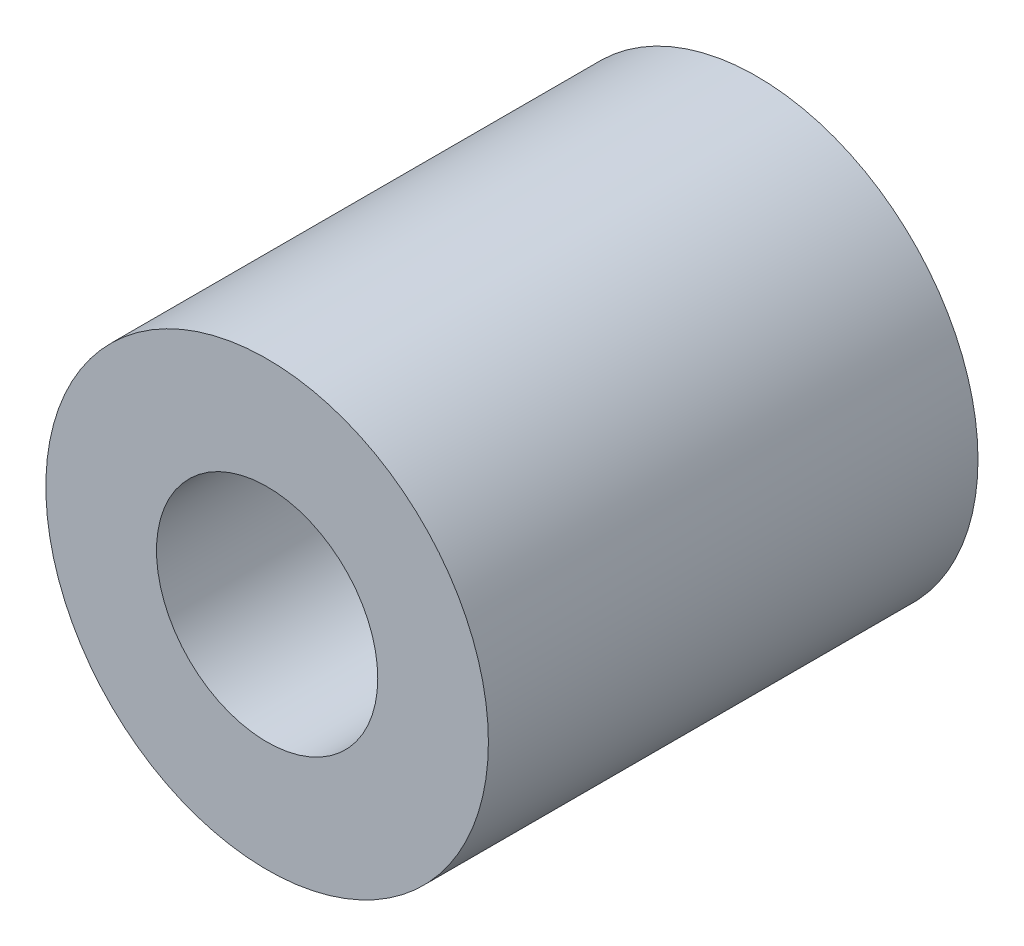
SolidWorks part; units mm, degrees
material "Nylon 101"
ref_plane "Front Plane" through (0, 0, 0) normal (0, 0, 1) x (1, 0, 0)
ref_plane "Top Plane" through (0, 0, 0) normal (0, 1, 0) x (1, 0, 0)
ref_plane "Right Plane" through (0, 0, 0) normal (1, 0, 0) x (0, 0, -1)
sketch "Sketch1" plane through (0, 0, 0) normal (0, 0, 1) x (1, 0, 0)
  circle A0 centre (0, 0) radius 6.35
  dimension "D1" = 12.7
extrude "Boss-Extrude1" add sketch "Sketch1" along normal blind 7.025 and the other way blind 7.025
sketch "Sketch2" plane through (0, 0, 7.025) normal (0, 0, 1) x (1, 0, 0)
  circle A0 centre (0, 0) radius 3.175
  dimension "D1" = 6.35
extrude "Cut-Extrude1" cut sketch "Sketch2" against normal through all
